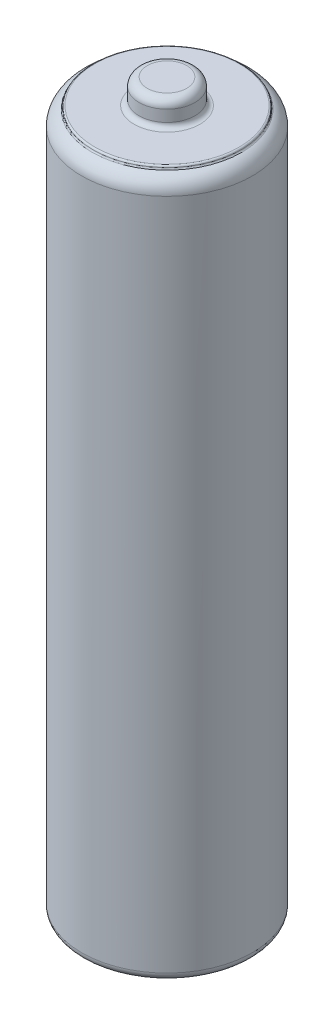
SolidWorks part; units mm, degrees
ref_plane "Front" through (0, 0, 0) normal (0, 0, 1) x (1, 0, 0)
ref_plane "Top" through (0, 0, 0) normal (0, 1, 0) x (1, 0, 0)
ref_plane "Right" through (0, 0, 0) normal (1, 0, 0) x (0, 0, -1)
sketch "Sketch1" plane through (0, 0, 0) normal (0, 1, 0) x (1, 0, 0)
  circle A0 centre (0, 0) radius 5.2
  dimension "D1" = 10.4
extrude "Boss-Extrude1" add sketch "Sketch1" along normal blind 42.4
sketch "Sketch2" plane through (0, 0, 0) normal (0, -1, 0) x (1, 0, 0)
  circle A0 centre (0, 0) radius 4.5
  dimension "D1" = 9
extrude "Boss-Extrude2" add sketch "Sketch2" along normal blind 0.3
sketch "Sketch3" plane through (0, 42.4, 0) normal (0, 1, 0) x (1, 0, 0)
  circle A0 centre (0, 0) radius 4.5
  dimension "D1" = 9
extrude "Boss-Extrude3" add sketch "Sketch3" along normal blind 0.2
sketch "Sketch4" plane through (0, 42.6, 0) normal (0, 1, 0) x (1, 0, 0)
  circle A0 centre (0, 0) radius 1.7
  dimension "D1" = 3.4
extrude "Boss-Extrude4" add sketch "Sketch4" along normal blind 1.5
fillet "Fillet1" radius 0.5 1 edges at (0, 44.1, 1.7)
fillet "Fillet2" radius 0.1 1 edges at (0, 42.4, 4.5)
fillet "Fillet3" radius 0.1 1 edges at (0, 42.6, 4.5)
fillet "Fillet4" radius 1 1 edges at (0, 42.4, 5.2)
fillet "Fillet7" radius 0.3 1 edges at (0, 42.6, 1.7)
fillet "Fillet8" radius 0.2 1 edges at (0, -0.3, -4.5)
fillet "Fillet9" radius 0.5 1 edges at (0, 0, 5.2)
